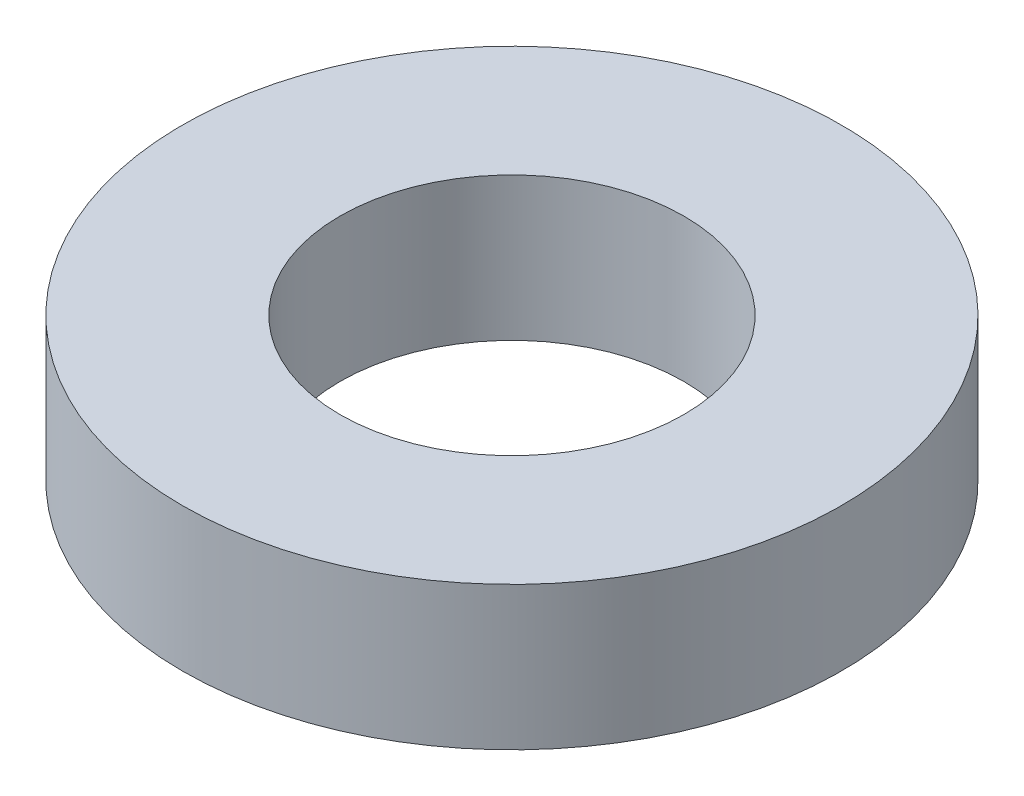
SolidWorks part; units mm, degrees
ref_plane "Front Plane" through (0, 0, 0) normal (0, 0, 1) x (1, 0, 0)
ref_plane "Top Plane" through (0, 0, 0) normal (0, 1, 0) x (1, 0, 0)
ref_plane "Right Plane" through (0, 0, 0) normal (1, 0, 0) x (0, 0, -1)
sketch "Sketch1" plane through (0, 0, 0) normal (0, 1, 0) x (1, 0, 0)
  circle A0 centre (0, 0) radius 57.5
  dimension "FLANGE_OD" = 115
extrude "Boss-Extrude1" add sketch "Sketch1" along normal blind 25
sketch "Sketch2" plane through (0, 0, 0) normal (0, 1, 0) x (1, 0, 0)
  circle A0 centre (0, 0) radius 30
  dimension "BORE_D" = 60
extrude "Cut-Extrude1" cut sketch "Sketch2" along normal through all
sketch "Sketch3" plane through (0, 25, 0) normal (0, 1, 0) x (1, 0, 0)
  circle A0 centre (0, 0) radius 19.9076 construction
  circle A1 centre (-19.9076, 0) radius 3.9647
  dimension "BOLT_D" = 7.9294
  dimension "BOLT_PCD" = 39.8151
extrude "Cut-Extrude2" cut sketch "Sketch3" against normal blind 21.413 rebuild error yes
pattern_circular "CirPattern1" count 3 over 360 rebuild error yes
